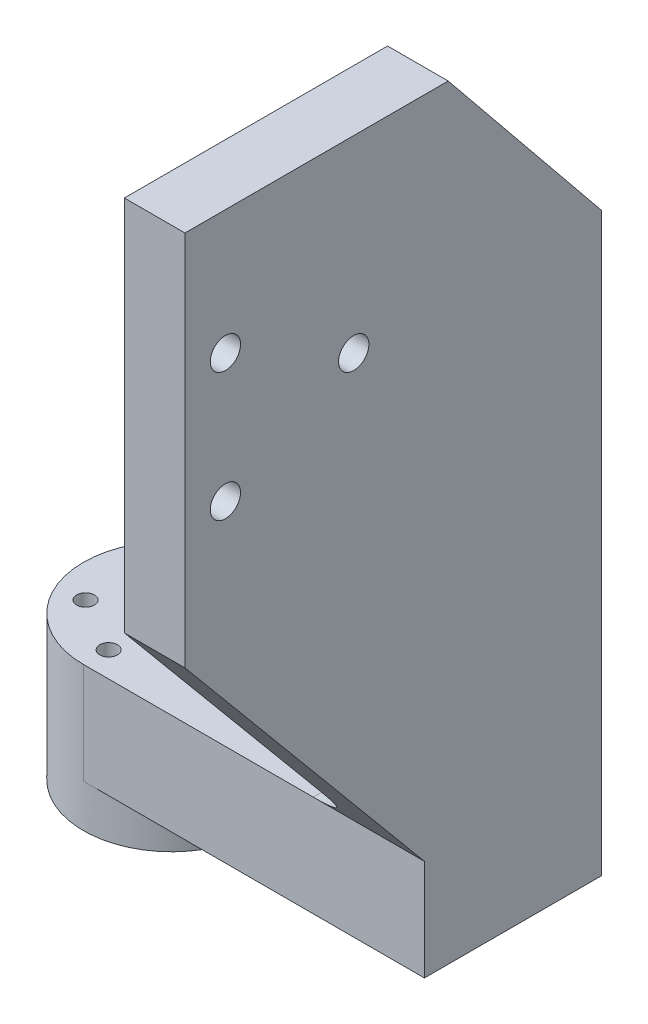
SolidWorks part; units mm, degrees
material "PLA"
ref_plane "Front Plane" through (0, 0, 0) normal (0, 0, 1) x (1, 0, 0)
ref_plane "Top Plane" through (0, 0, 0) normal (0, 1, 0) x (1, 0, 0)
ref_plane "Right Plane" through (0, 0, 0) normal (1, 0, 0) x (0, 0, -1)
sketch "Sketch1" plane through (0, 0, 0) normal (0, 1, 0) x (1, 0, 0)
  line L0 (0, 17.5) -> (67.5, 17.5)
  line L1 (0, -17.5) -> (67.5, -17.5)
  line L2 (67.5, -17.5) -> (67.5, 17.5)
  circle A0 centre (0, 0) radius 17.5
  dimension "D1" = 35
  dimension "D2" = 67.5
extrude "Boss-Extrude1" add sketch "Sketch1" along normal blind 20 contours A0 | A0 L1 L2 L0 region at (40.4803, 0, 0) region at (0, 0, 0)
sketch "Sketch2" plane through (0, 0, 0) normal (0, -1, 0) x (1, 0, 0)
  circle A0 centre (0, 0) radius 17.5 construction
  circle A1 centre (0, 0) radius 17.5
extrude "Boss-Extrude2" add sketch "Sketch2" along normal blind 8.5
sketch "Sketch3" plane through (67.5, 0, 0) normal (1, 0, 0) x (0, 0, -1)
  line L0 (17.5, 0) -> (17.5, 20)
  line L1 (-17.5, 20) -> (-57.39, 67.85)
  line L2 (17.5, 20) -> (17.5, 67.85) construction
  line L3 (17.5, 67.85) -> (-57.39, 67.85) construction
  line L4 (17.5, 20) -> (-12.79, 67.85) construction
  line L5 (-12.79, 67.85) -> (-57.39, 67.85)
  line L6 (17.5, 0) -> (-17.5, 0)
  line L7 (-17.5, 0) -> (17.5, 0) construction
  line L8 (-17.5, 0) -> (-17.5, 20)
  line L9 (-57.39, 67.85) -> (-64.89, 76.8466)
  line L10 (-57.39, 67.85) -> (-64.89, 67.85)
  line L11 (-64.89, 76.8466) -> (-64.89, 151.39)
  line L12 (-64.89, 151.39) -> (-12.79, 151.39)
  line L13 (-12.79, 151.39) -> (-12.79, 67.85) construction
  line L14 (17.5, 20) -> (17.5, 114.1183)
  line L15 (-12.79, 151.39) -> (17.5, 114.1183)
  point P19 (-64.89, 114.1183)
  line M1 (-17.5, 0) -> (17.5, 0)
  line M2 (17.5, 0) -> (17.5, 20)
  line M3 (17.5, 20) -> (-17.5, 20)
  line M4 (-17.5, 20) -> (-17.5, 0)
  dimension "D1" = 47.85
  dimension "D2" = 74.89
  dimension "D3" = 30.29
  dimension "D4" = 7.5
  dimension "D5" = 83.54
extrude "Boss-Extrude3" add sketch "Sketch3" against normal blind 12 contours L13 L12 L11 L9 L5 | L4 L5 L1 M3 | M4 M1 M2 M3 region at (67.5, 10, 0) region at (67.5, 89.3854, 21.8264)
sketch "Sketch4" plane through (67.5, 0, 0) normal (1, 0, 0) x (0, 0, -1)
  line L0 (-56.89, 126.8183) -> (-56.89, 101.4183) construction
  line L1 (-64.89, 76.8466) -> (-64.89, 151.39) construction
  line L2 (-56.89, 114.1183) -> (-31.49, 114.1183) construction
  circle A0 centre (-56.89, 101.4183) radius 3
  circle A1 centre (-56.89, 126.8183) radius 3
  circle A2 centre (-31.49, 114.1183) radius 3
  point P4 (-64.89, 114.1183)
  point P5 (-56.89, 114.1183)
  dimension "D3" = 6
  dimension "D4" = 6
  dimension "D6" = 6
  dimension "D1" = 25.4
  dimension "D2" = 8
  dimension "D5" = 25.4
extrude "Cut-Extrude1" cut sketch "Sketch4" against normal through all
sketch "Sketch5" plane through (0, -8.5, 0) normal (0, -1, 0) x (1, 0, 0)
  line L0 (0, 0) -> (0, 12.5) construction
  circle A0 centre (0, 12.5) radius 1.75
  circle A1 centre (10.8253, 6.25) radius 1.75
  circle A2 centre (10.8253, -6.25) radius 1.75
  circle A3 centre (0, -12.5) radius 1.75
  circle A4 centre (-10.8253, -6.25) radius 1.75
  circle A5 centre (-10.8253, 6.25) radius 1.75
  point P16 (0, 0)
  dimension "D2" = 3.5
  dimension "D1" = 12.5
  dimension "D3" = 6
extrude "Cut-Extrude2" cut sketch "Sketch5" against normal through all
fillet "Fillet1" radius 10 1 edges at (55.5, 20, 0)
ref_plane "Plane1" through (-20, 0, 0) normal (1, 0, 0) x (0, 0, -1)
mirror "Mirror1" about plane through (-20, 0, 0) normal (1, 0, 0) of bodies 105
delete or keep bodies "Body-Delete/Keep 1" type delete bodies bodies 106
